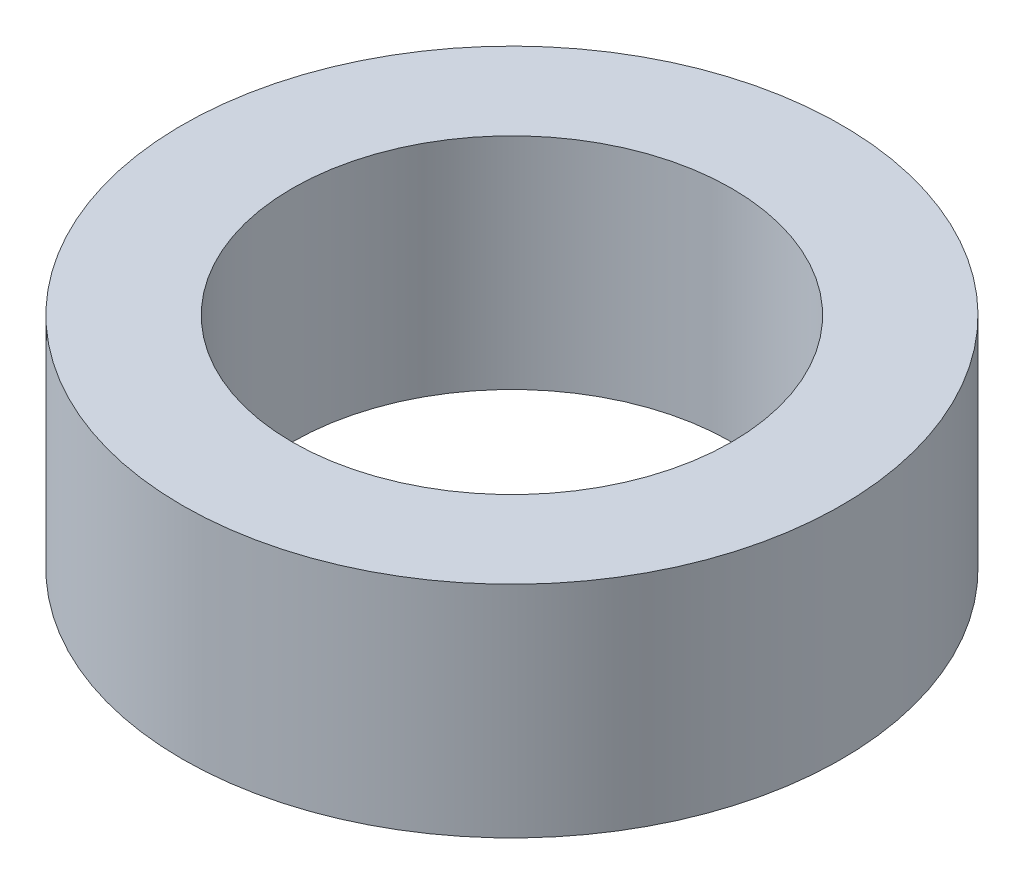
SolidWorks part; units mm, degrees
material "Rubber"
ref_plane "Front Plane" through (0, 0, 0) normal (0, 0, 1) x (1, 0, 0)
ref_plane "Top Plane" through (0, 0, 0) normal (0, 1, 0) x (1, 0, 0)
ref_plane "Right Plane" through (0, 0, 0) normal (1, 0, 0) x (0, 0, -1)
sketch "Sketch1" plane through (0, 0, 0) normal (0, 1, 0) x (1, 0, 0)
  circle A0 centre (0, 0) radius 12.7
  circle A1 centre (0, 0) radius 19.05
  dimension "D1" = 25.4
  dimension "D2" = 38.1
extrude "Boss-Extrude1" add sketch "Sketch1" along normal blind 12.7
